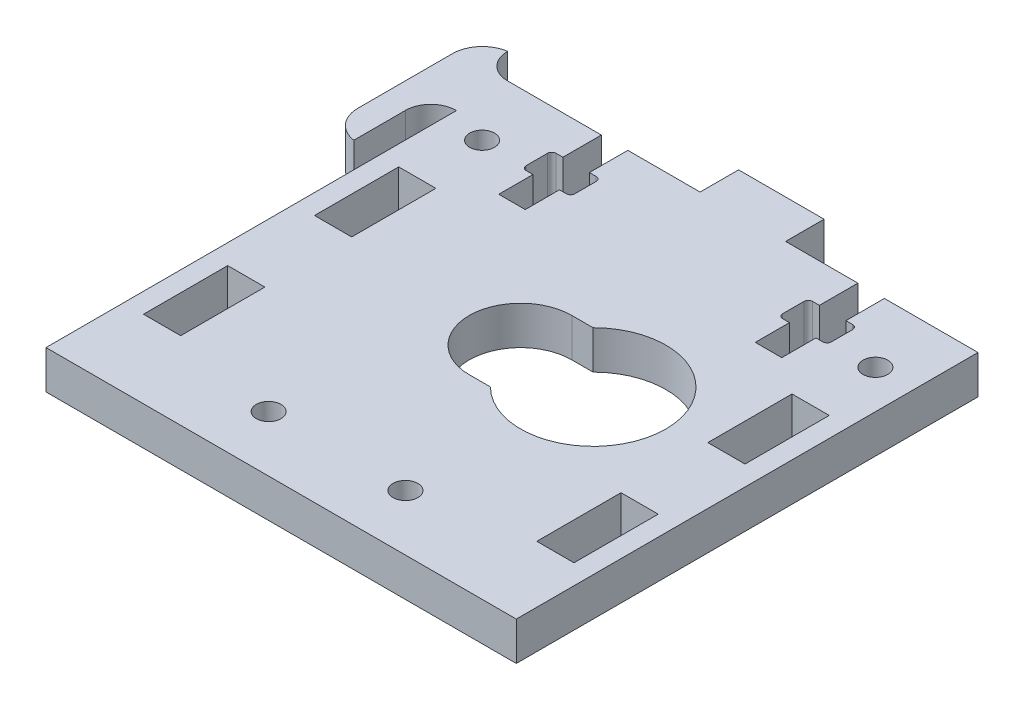
SolidWorks part; units mm, degrees
ref_plane "Front Plane" through (0, 0, 0) normal (0, 0, 1) x (1, 0, 0)
ref_plane "Top Plane" through (0, 0, 0) normal (0, 1, 0) x (1, 0, 0)
ref_plane "Right Plane" through (0, 0, 0) normal (1, 0, 0) x (0, 0, -1)
sketch "Sketch1" plane through (0, 0, 0) normal (0, 1, 0) x (1, 0, 0)
  line L1 (-27.5, 27) -> (27.5, 27)
  line L2 (-27.5, 27) -> (-27.5, -27)
  line L3 (-27.5, -27) -> (27.5, -27)
  line L4 (27.5, 27) -> (27.5, -27)
  line L5 (-27.5, 27) -> (27.5, -27) construction
  line L6 (-27.5, -27) -> (27.5, 27) construction
  point P0 (0, 0)
  dimension "D1" = 55
  dimension "D2" = 54
extrude "MainShape" add sketch "Sketch1" along normal blind 4.5
sketch "Sketch2" plane through (0, 4.5, 0) normal (0, 1, 0) x (1, 0, 0)
  line L0 (0, -27) -> (0, 27) construction
  line L1 (-27.5, -27) -> (27.5, -27) construction
  line L2 (27.5, 27) -> (-27.5, 27) construction
  line L4 (-5, 31.5) -> (5, 31.5)
  line L5 (-5, 31.5) -> (-5, 22.5)
  line L6 (-5, 22.5) -> (5, 22.5)
  line L7 (5, 31.5) -> (5, 22.5)
  line L8 (-5, 31.5) -> (5, 22.5) construction
  line L9 (-5, 22.5) -> (5, 31.5) construction
  dimension "D1" = 10
  dimension "D2" = 4.5
extrude "Tab1" add sketch "Sketch2" against normal through all
sketch "Sketch4" plane through (0, 4.5, 0) normal (0, 1, 0) x (1, 0, 0)
  line L0 (0, 31.5) -> (0, -27) construction
  line L1 (5, 31.5) -> (-5, 31.5) construction
  line L2 (-27.5, -27) -> (27.5, -27) construction
  line L3 (-15, 27) -> (-15, 15) construction
  line L4 (-5, 27) -> (-27.5, 27) construction
  line L5 (-13.45, 15) -> (-16.55, 15) construction
  line L6 (-16.55, 15) -> (-16.55, 27) construction
  line L7 (-13.45, 15) -> (-16.55, 15)
  line L8 (-16.55, 15) -> (-16.55, 19)
  line L9 (-16.55, 19) -> (-17.35, 19)
  line L10 (-17.85, 19.5) -> (-17.85, 22)
  line L11 (-17.35, 22.5) -> (-16.55, 22.5)
  line L12 (-16.55, 22.5) -> (-16.55, 27)
  line L13 (-16.55, 27) -> (-13.45, 27)
  line L14 (-13.45, 15) -> (-13.45, 27) construction
  line L15 (-13.45, 22.5) -> (-13.45, 27)
  line L16 (-12.65, 22.5) -> (-13.45, 22.5)
  line L17 (-12.15, 19.5) -> (-12.15, 22)
  line L18 (-13.45, 19) -> (-12.65, 19)
  line L19 (-13.45, 15) -> (-13.45, 19)
  line L20 (13.45, 15) -> (13.45, 27) construction
  line L21 (16.55, 15) -> (16.55, 27) construction
  line L22 (13.45, 15) -> (16.55, 15) construction
  line L23 (15, 27) -> (15, 15) construction
  line L24 (13.45, 15) -> (13.45, 19)
  line L25 (13.45, 19) -> (12.65, 19)
  line L26 (12.15, 19.5) -> (12.15, 22)
  line L27 (12.65, 22.5) -> (13.45, 22.5)
  line L28 (13.45, 22.5) -> (13.45, 27)
  line L29 (16.55, 27) -> (13.45, 27)
  line L30 (16.55, 22.5) -> (16.55, 27)
  line L31 (17.35, 22.5) -> (16.55, 22.5)
  line L32 (17.85, 19.5) -> (17.85, 22)
  line L33 (16.55, 19) -> (17.35, 19)
  line L34 (16.55, 15) -> (16.55, 19)
  line L35 (13.45, 15) -> (16.55, 15)
  arc A0 (-17.35, 19) -> (-17.85, 19.5) centre (-17.35, 19.5) cw
  arc A1 (-12.15, 19.5) -> (-12.65, 19) centre (-12.65, 19.5) cw
  arc A2 (-12.65, 22.5) -> (-12.15, 22) centre (-12.65, 22) cw
  arc A3 (-17.85, 22) -> (-17.35, 22.5) centre (-17.35, 22) cw
  arc A4 (17.85, 22) -> (17.35, 22.5) centre (17.35, 22) ccw
  arc A5 (12.65, 22.5) -> (12.15, 22) centre (12.65, 22) ccw
  arc A6 (12.15, 19.5) -> (12.65, 19) centre (12.65, 19.5) ccw
  arc A7 (17.35, 19) -> (17.85, 19.5) centre (17.35, 19.5) ccw
  point P24 (-17.85, 19)
  point P27 (-12.15, 19)
  point P30 (-12.15, 22.5)
  point P33 (-17.85, 22.5)
  point P56 (17.85, 22.5)
  point P57 (12.15, 22.5)
  point P58 (12.15, 19)
  point P59 (17.85, 19)
  dimension "D7" = 0.5
  dimension "D1" = 12
  dimension "D2" = 1.55
  dimension "D3" = 3.5
  dimension "D4" = 2.85
  dimension "D5" = 8
  dimension "D6" = 15
extrude "Cut-Extrude2" cut sketch "Sketch4" against normal through all
sketch "Sketch5" plane through (0, 4.5, 0) normal (0, 1, 0) x (1, 0, 0)
  line L0 (0, -27) -> (0, 31.5) construction
  line L1 (-27.5, -27) -> (27.5, -27) construction
  line L2 (5, 31.5) -> (-5, 31.5) construction
  line L3 (23, 27) -> (23, -27) construction
  line L4 (27.5, 27) -> (16.55, 27) construction
  line L5 (-23, 27) -> (-23, -27) construction
  line L6 (20.825, 11.925) -> (25.175, 11.925)
  line L7 (20.825, 11.925) -> (20.825, 2.075)
  line L8 (20.825, 2.075) -> (25.175, 2.075)
  line L9 (25.175, 11.925) -> (25.175, 2.075)
  line L10 (20.825, 11.925) -> (25.175, 2.075) construction
  line L11 (20.825, 2.075) -> (25.175, 11.925) construction
  line L12 (-20.825, 2.075) -> (-25.175, 11.925) construction
  line L13 (-20.825, 11.925) -> (-25.175, 2.075) construction
  line L14 (-25.175, 11.925) -> (-25.175, 2.075)
  line L15 (-20.825, 2.075) -> (-25.175, 2.075)
  line L16 (-20.825, 11.925) -> (-20.825, 2.075)
  line L17 (-20.825, 11.925) -> (-25.175, 11.925)
  line L18 (-27.5, -3) -> (27.5, -3) construction
  line L19 (-27.5, 27) -> (-27.5, -27) construction
  line L20 (27.5, -27) -> (27.5, 27) construction
  line L21 (-20.825, -17.925) -> (-25.175, -8.075) construction
  line L22 (-20.825, -8.075) -> (-25.175, -17.925) construction
  line L23 (20.825, -8.075) -> (25.175, -17.925) construction
  line L24 (20.825, -17.925) -> (25.175, -8.075) construction
  line L25 (-20.825, -17.925) -> (-25.175, -17.925)
  line L26 (-20.825, -17.925) -> (-20.825, -8.075)
  line L27 (-20.825, -8.075) -> (-25.175, -8.075)
  line L28 (-25.175, -17.925) -> (-25.175, -8.075)
  line L29 (25.175, -17.925) -> (25.175, -8.075)
  line L30 (20.825, -8.075) -> (25.175, -8.075)
  line L31 (20.825, -17.925) -> (20.825, -8.075)
  line L32 (20.825, -17.925) -> (25.175, -17.925)
  line L33 (-20.825, 11.925) -> (-25.175, 2.075) construction
  point P10 (23, 7)
  point P21 (-23, 7)
  point P36 (-23, -13)
  point P37 (23, -13)
  dimension "D1" = 23
  dimension "D2" = 9.85
  dimension "D3" = 4.35
  dimension "D4" = 20
  dimension "D5" = 20
extrude "Cut-Extrude3" cut sketch "Sketch5" against normal through all
sketch "Sketch6" plane through (0, 4.5, 0) normal (0, 1, 0) x (1, 0, 0)
  line L0 (0, -27) -> (0, 27) construction
  line L1 (5, 31.5) -> (-5, 31.5) construction
  line L3 (-27.5, 1) -> (27.5, 1) construction
  line L4 (-27.5, 27) -> (-27.5, -27) construction
  line L5 (27.5, -27) -> (27.5, 27) construction
  line L6 (27.5, 27) -> (16.55, 27) construction
  line L7 (-27.5, -27) -> (27.5, -27) construction
  line L9 (-27.5, 27) -> (27.5, 27) construction
  circle A0 centre (0, 1) radius 12
  point P4 (0, 31.5)
  dimension "D1" = 24
  dimension "D2" = 26
extrude "Cut-Extrude4" cut sketch "Sketch6" against normal through all
sketch "Sketch7" plane through (0, 4.5, 0) normal (0, 1, 0) x (1, 0, 0)
  line L0 (0, 1) -> (0, -27) construction
  line L3 (-27.5, -27) -> (27.5, -27) construction
  line L4 (8, -20.46) -> (-8, -20.46) construction
  circle A1 centre (-8, -20.46) radius 1.45
  circle A2 centre (8, -20.46) radius 1.45
  point P8 (0, -20.46)
  dimension "D1" = 2.9
  dimension "D3" = 21.46
extrude "Cut-Extrude5" [suppressed] cut sketch "Sketch7" against normal through all
sketch "Sketch8" plane through (0, 4.5, 0) normal (0, 1, 0) x (1, 0, 0)
  line L0 (-12, 1) -> (12, 1) construction
  line L1 (0, 1) -> (0, -20.46) construction
  line L2 (8, -20.46) -> (-8, -20.46) construction
  line L3 (0, -11) -> (0, 13) construction
  circle A0 centre (-8, -20.46) radius 1.45
  circle A1 centre (0, 1) radius 12 construction
  circle A2 centre (8, -20.46) radius 1.45
  dimension "D3" = 2.9
  dimension "D1" = 90
  dimension "D4" = 21.46
extrude "Cut-Extrude6" cut sketch "Sketch8" against normal through all
sketch "Sketch9" plane through (0, 4.5, 0) normal (0, 1, 0) x (1, 0, 0)
  line L0 (0, -27) -> (0, 31.5) construction
  line L1 (-27.5, -27) -> (27.5, -27) construction
  line L2 (5, 31.5) -> (-5, 31.5) construction
  line L3 (16, -27) -> (16, -16) construction
  line L4 (14.45, -16) -> (17.55, -16) construction
  line L5 (17.55, -16) -> (17.55, -27) construction
  line L6 (17.55, -27) -> (17.55, -22.5)
  line L7 (17.55, -22.5) -> (18.35, -22.5)
  line L8 (18.85, -22) -> (18.85, -19.5)
  line L9 (18.35, -19) -> (17.55, -19)
  line L10 (17.55, -19) -> (17.55, -16)
  line L11 (17.55, -16) -> (14.45, -16)
  line L12 (17.55, -27) -> (14.45, -27)
  line L13 (14.45, -16) -> (14.45, -27) construction
  line L14 (14.45, -19) -> (14.45, -16)
  line L15 (13.65, -19) -> (14.45, -19)
  line L16 (13.15, -22) -> (13.15, -19.5)
  line L17 (14.45, -22.5) -> (13.65, -22.5)
  line L18 (14.45, -27) -> (14.45, -22.5)
  line L19 (-14.45, -16) -> (-14.45, -27) construction
  line L20 (-17.55, -16) -> (-17.55, -27) construction
  line L21 (-14.45, -16) -> (-17.55, -16) construction
  line L22 (-16, -27) -> (-16, -16) construction
  line L23 (-14.45, -27) -> (-14.45, -22.5)
  line L24 (-14.45, -22.5) -> (-13.65, -22.5)
  line L25 (-13.15, -22) -> (-13.15, -19.5)
  line L26 (-13.65, -19) -> (-14.45, -19)
  line L27 (-14.45, -19) -> (-14.45, -16)
  line L28 (-17.55, -27) -> (-14.45, -27)
  line L29 (-17.55, -16) -> (-14.45, -16)
  line L30 (-17.55, -19) -> (-17.55, -16)
  line L31 (-18.35, -19) -> (-17.55, -19)
  line L32 (-18.85, -22) -> (-18.85, -19.5)
  line L33 (-17.55, -22.5) -> (-18.35, -22.5)
  line L34 (-17.55, -27) -> (-17.55, -22.5)
  arc A0 (18.35, -22.5) -> (18.85, -22) centre (18.35, -22) ccw
  arc A1 (18.85, -19.5) -> (18.35, -19) centre (18.35, -19.5) ccw
  arc A2 (13.15, -19.5) -> (13.65, -19) centre (13.65, -19.5) cw
  arc A3 (13.65, -22.5) -> (13.15, -22) centre (13.65, -22) cw
  arc A4 (-13.65, -22.5) -> (-13.15, -22) centre (-13.65, -22) ccw
  arc A5 (-13.15, -19.5) -> (-13.65, -19) centre (-13.65, -19.5) ccw
  arc A6 (-18.85, -19.5) -> (-18.35, -19) centre (-18.35, -19.5) cw
  arc A7 (-18.35, -22.5) -> (-18.85, -22) centre (-18.35, -22) cw
  point P16 (18.85, -22.5)
  point P19 (18.85, -19)
  point P30 (13.15, -19)
  point P31 (13.15, -22.5)
  point P54 (-13.15, -22.5)
  point P55 (-13.15, -19)
  point P56 (-18.85, -19)
  point P57 (-18.85, -22.5)
  dimension "D7" = 0.5
  dimension "D2" = 1.55
  dimension "D1" = 11
  dimension "D3" = 8
  dimension "D4" = 3.5
  dimension "D5" = 2.85
  dimension "D6" = 16
extrude "Cut-Extrude7" [suppressed] cut sketch "Sketch9" against normal through all
sketch "Sketch10" [suppressed] plane through (0, 0, 27) normal (0, 0, 1) x (1, 0, 0)
  line L0 (-27.5, 2.25) -> (27.5, 2.25) construction
  line L1 (-27.5, 4.5) -> (-27.5, 0) construction
  line L2 (27.5, 4.5) -> (27.5, 0) construction
  line L3 (-16, 4.5) -> (-16, 0) construction
  line L4 (-14.25, 4.5) -> (-17.75, 4.5) construction
  line L5 (16, 4.5) -> (16, 0) construction
  line L6 (17.75, 4.5) -> (14.25, 4.5) construction
  line L7 (17.75, 0) -> (14.25, 0) construction
  line L8 (-14.25, 0) -> (-17.75, 0) construction
  circle A0 centre (-16, 2.25) radius 1.6
  circle A1 centre (16, 2.25) radius 1.6
  dimension "D1" = 3.2
  dimension "D2" = 3.2
sketch "Sketch11" plane through (0, 4.5, 0) normal (0, 1, 0) x (1, 0, 0)
  line L0 (-20.825, 7) -> (-25.175, 7) construction
  line L1 (-20.825, 2.075) -> (-20.825, 11.925) construction
  line L2 (-25.175, 11.925) -> (-25.175, 2.075) construction
  line L3 (-23, 7) -> (-23, 27) construction
  line L4 (-16.55, 27) -> (-27.5, 27) construction
  line L5 (0, 31.5) -> (0, 0) construction
  line L6 (5, 31.5) -> (-5, 31.5) construction
  line L7 (23, 7) -> (23, 27) construction
  line L8 (20.825, 7) -> (25.175, 7) construction
  line L9 (-23, 7) -> (-23, 27) construction
  circle A0 centre (-23, 19.5) radius 1.45
  circle A1 centre (23, 19.5) radius 1.45
  dimension "D1" = 2.9
  dimension "D2" = 7.5
extrude "Cut-Extrude8" cut sketch "Sketch11" against normal through all
sketch "Sketch12" [suppressed] plane through (0, 4.5, 0) normal (0, 1, 0) x (1, 0, 0)
  line L0 (-27.5, -7) -> (-34, -17)
  line L1 (-27.5, 27) -> (-27.5, -27) construction
  line L2 (-34, -17) -> (-34, -27)
  line L3 (-34, -27) -> (-27.5, -27)
  line L4 (-27.5, -27) -> (-27.5, -7)
  line L5 (-27.5, -27) -> (27.5, -27) construction
  line L6 (0, -27) -> (0, 31.5) construction
  line L7 (5, 31.5) -> (-5, 31.5) construction
  line L8 (27.5, -27) -> (27.5, -7)
  line L9 (34, -27) -> (27.5, -27)
  line L10 (34, -17) -> (34, -27)
  line L11 (27.5, -7) -> (34, -17)
  point P4 (0, -27)
  dimension "D1" = 34
  dimension "D2" = 10
  dimension "D3" = 20
extrude "Boss-Extrude1" [suppressed] add sketch "Sketch12" against normal through all
sketch "Sketch14" [suppressed] plane through (0, 4.5, 0) normal (0, 1, 0) x (1, 0, 0)
  line L0 (-34, -27) -> (34, -27) construction
  line L2 (-34, -27) -> (34, -27) construction
  line L3 (0, -27) -> (0, 31.5) construction
  line L4 (5, 31.5) -> (-5, 31.5) construction
  line L6 (26.25, -16.5) -> (26.25, -27) construction
  line L8 (-28, -27) -> (-28, -16.5) construction
  line L9 (-26.25, -16.5) -> (-29.75, -16.5) construction
  line L10 (-29.75, -16.5) -> (-29.75, -27) construction
  line L11 (-26.25, -27) -> (-29.75, -27)
  line L12 (-29.75, -27) -> (-29.75, -23.2)
  line L13 (-29.75, -23.2) -> (-30.75, -23.2)
  line L14 (-31, -22.95) -> (-31, -19.25)
  line L15 (-30.75, -19) -> (-29.75, -19)
  line L16 (-29.75, -19) -> (-29.75, -16.5)
  line L17 (-29.75, -16.5) -> (-26.25, -16.5)
  line L18 (-26.25, -16.5) -> (-26.25, -27) construction
  line L19 (-26.25, -19) -> (-26.25, -16.5)
  line L20 (-25.25, -19) -> (-26.25, -19)
  line L21 (-25, -22.95) -> (-25, -19.25)
  line L22 (-26.25, -23.2) -> (-25.25, -23.2)
  line L23 (-26.25, -27) -> (-26.25, -23.2)
  line L24 (29.75, -16.5) -> (29.75, -27) construction
  line L25 (26.25, -16.5) -> (29.75, -16.5) construction
  line L26 (28, -27) -> (28, -16.5) construction
  line L27 (26.25, -27) -> (26.25, -23.2)
  line L28 (26.25, -23.2) -> (25.25, -23.2)
  line L29 (25, -22.95) -> (25, -19.25)
  line L30 (25.25, -19) -> (26.25, -19)
  line L31 (26.25, -19) -> (26.25, -16.5)
  line L32 (29.75, -16.5) -> (26.25, -16.5)
  line L33 (29.75, -19) -> (29.75, -16.5)
  line L34 (30.75, -19) -> (29.75, -19)
  line L35 (31, -22.95) -> (31, -19.25)
  line L36 (29.75, -23.2) -> (30.75, -23.2)
  line L37 (29.75, -27) -> (29.75, -23.2)
  line L38 (26.25, -27) -> (29.75, -27)
  line L39 (-26.25, -16.5) -> (-26.25, -27) construction
  arc A0 (-30.75, -23.2) -> (-31, -22.95) centre (-30.75, -22.95) cw
  arc A1 (-31, -19.25) -> (-30.75, -19) centre (-30.75, -19.25) cw
  arc A2 (-25, -19.25) -> (-25.25, -19) centre (-25.25, -19.25) ccw
  arc A3 (-25.25, -23.2) -> (-25, -22.95) centre (-25.25, -22.95) ccw
  arc A4 (25.25, -23.2) -> (25, -22.95) centre (25.25, -22.95) cw
  arc A5 (25, -19.25) -> (25.25, -19) centre (25.25, -19.25) cw
  arc A6 (31, -19.25) -> (30.75, -19) centre (30.75, -19.25) ccw
  arc A7 (30.75, -23.2) -> (31, -22.95) centre (30.75, -22.95) ccw
  point P2 (0, -27)
  dimension "D10" = 0.5
  dimension "D4" = 1.55
  dimension "D6" = 11
  dimension "D2" = 28
  dimension "D3" = 2.85
  dimension "D5" = 3.5
  dimension "D7" = 8
extrude "Cut-Extrude9" [suppressed] cut sketch "Sketch14" against normal through all
sketch "Sketch15" plane through (0, 4.5, 0) normal (0, 1, 0) x (1, 0, 0)
  circle A0 centre (0, 1) radius 12
  circle A1 centre (0, 1) radius 6
  circle A2 centre (0, 1) radius 12 construction
  dimension "D1" = 12
extrude "Boss-Extrude2" add sketch "Sketch15" against normal through all
sketch "Sketch16" plane through (0, 4.5, 0) normal (0, 1, 0) x (1, 0, 0)
  line L0 (0, 1) -> (27.5, 1) construction
  line L1 (27.5, -27) -> (27.5, 27) construction
  line L2 (0, 7) -> (2.4792, 7)
  line L3 (0, -5) -> (2.4792, -5)
  line L4 (0, 7) -> (0, -5)
  arc A0 (2.4792, -5) -> (2.4792, 7) centre (8.5, 1) ccw
  circle A1 centre (0, 1) radius 6 construction
  dimension "D1" = 17
  dimension "D2" = 8.5
extrude "Cut-Extrude10" cut sketch "Sketch16" against normal through all
sketch "Sketch17" plane through (0, 4.5, 0) normal (0, 1, 0) x (1, 0, 0)
  line L0 (-27.5, 22) -> (-27.5, 18) construction
  line L1 (-27.5, 27) -> (-27.5, -27) construction
  line L2 (-27.5, 25.5) -> (-27.5, 23.5)
  line L3 (-29, 22) -> (-29, 18)
  line L4 (-27.5, 22) -> (-27.5, 18) construction
  line L5 (-27.5, 16.5) -> (-27.5, 14.5)
  line L6 (-31, 22) -> (-31, 18)
  line L7 (-27.5, 25.5) -> (-27.5, 14.5) construction
  arc A0 (-27.5, 23.5) -> (-29, 22) centre (-27.5, 22) ccw
  arc A1 (-29, 18) -> (-27.5, 16.5) centre (-27.5, 18) ccw
  arc A2 (-27.5, 25.5) -> (-31, 22) centre (-27.5, 22) ccw
  arc A3 (-31, 18) -> (-27.5, 14.5) centre (-27.5, 18) ccw
  point P10 (-27.5, 20)
  dimension "D1" = 1.5
  dimension "D2" = 1.5
  dimension "D3" = 2
  dimension "D4" = 4
  dimension "D5" = 20
  dimension "D7" = 2
extrude "CableTieSlot" [suppressed] add sketch "Sketch17" against normal through all
sketch "Sketch18" plane through (0, 4.5, 0) normal (0, 1, 0) x (1, 0, 0)
  line L0 (-27.5, 27) -> (-27.55, 27)
  line L1 (-33.5, 30) -> (-33.5, 12)
  line L2 (-33.5, 12) -> (-30.5, 12)
  line L3 (-30.5, 12) -> (-30.5, 18.05)
  line L4 (-27.55, 21) -> (-27.5, 21)
  line L5 (-27.5, 27) -> (-27.5, -27) construction
  line L6 (-27.5, 21) -> (-27.5, 27)
  line L7 (-16.55, 27) -> (-27.5, 27) construction
  line L8 (-33.5, 30) -> (-30.5, 30)
  line L9 (-30.5, 30) -> (-30.5, 29.95)
  arc A0 (-27.55, 27) -> (-30.5, 29.95) centre (-27.55, 29.95) cw
  arc A1 (-30.5, 18.05) -> (-27.55, 21) centre (-27.55, 18.05) cw
  point P17 (-30.5, 27)
  dimension "D1" = 2.95
  dimension "D2" = 2.95
  dimension "D3" = 6
  dimension "D4" = 3
  dimension "D5" = 15
  dimension "D6" = 3
  dimension "D7" = 3
extrude "Boss-Extrude3" add sketch "Sketch18" against normal through all
fillet "Fillet1" radius 3.5 2 edges at (-33.5, 2.25, -30) (-33.5, 2.25, -12)
equation "\"X-ROD-SPACING\"=45"
equation "\"Y-ROD-SPACING\"=75"
equation "\"Z-ROD-SPACING\"=17.5"
equation "\"Y-BED-OFFSET\"=2"
equation "\"Y-BED-ROD-INSET\"=3.5"
equation "\"Y-BED-SCREW-SPACING\"=209"
equation "\"Y-BED-SCREW-CUTOUT-SLOT-HEIGHT\"=2.5"
equation "\"T-SLOT-NUT-FILLET-RADIUS\"=0.5"
equation "\"T-SLOT-SCREW-SHAFT-RADIUS\"=1.55"
equation "\"T-SLOT-SCREW-SHAFT-CUTOUT-LENGTH\"=11"
equation "\"T-SLOT-NUT-DEPTH\"=3.5"
equation "\"T-SLOT-NUT-WIDTH\"=2.85"
equation "\"T-SLOT-NUT-END-DISTANCE\"=8"
equation "\"ACRYLIC-THICKNESS\"=10"
equation "\"ACRYLIC-THICKNESS2\"=4.5"
equation "\"ACRYLIC-TAB-CUTOUT-SIZE\"=\"ACRYLIC-THICKNESS\"+\"ACRYLIC-TAB-TOLERANCE\"*2"
equation "\"ACRYLIC-TAB-WIDTH\"=\"ACRYLIC-THICKNESS\""
equation "\"ACRYLIC-M3-HOLE\"=2.9"
equation "\"SMOOTHROD-CAP-SCREW-DISTANCE\"=20"
equation "\"FRAME-WIDTH-INNER\"=370"
equation "\"NEMA17-HOLE-SPACING\"=31"
equation "\"NEMA17-CENTRAL-CUTOUT\"=22.5"
equation "\"Z-BRACKET-REACH\"=57"
equation "\"Z-ROD-INSET\"=13.5"
equation "\"TOP-BRACKET-SPACING\"=40"
equation "\"SMOOTHROD-X-LENGTH\"=350"
equation "\"SMOOTHROD-Y-LENGTH\"=350"
equation "\"SMOOTHROD-Z-LENGTH\"=350"
equation "\"SMOOTHROD-TIGHTENING-HEADROOM\"=.25"
equation "\"LEADSCREW-Z-LENGTH\"=300"
equation "\"SCREW-LENGTH-FRAME\"=\"ACRYLIC-THICKNESS\" + 10"
equation "\"SCREW-LENGTH-MOTOR\"=\"ACRYLIC-THICKNESS\" + 5"
equation "\"SCREW-LENGTH-EXTRUDER\"=28"
equation "\"SCREW-HEAD-RADIUS\"=6"
equation "\"PRINTED-X-SMOOTHROD-DIAMETER\"=8.8"
equation "\"PRINTED-X-SMOOTHROD-CUTOUT\"=10"
equation "\"PRINTED-X-BASE-HEIGHT\"=10"
equation "\"PRINTED-LM8UU-CUTOUT-SIZE\"=15.5"
equation "\"PRINTED-LM8UU-CUTOUT-LENGTH\"=24.5"
equation "\"PRINTED-X-IDLER-HEIGHT\"=16"
equation "\"PSU-MOUNTING-WIDTH\"=50"
equation "\"PSU-MOUNTING-HEIGHT\"=150"
equation "\"Y-BELT-TO-ROD-DISTANCE\"=20"
equation "\"SPOOL-HOLDER-ROD-SPACING\"=150"
equation "\"ACRYLIC-X-CARRIAGE-WIDTH\"=55"
equation "\"ACRYLIC-X-CARRIAGE-HEIGHT\"=75"
equation "\"ACRYLIC-X-CARRIAGE-SCREW-SPACING-X\"=15"
equation "\"ACRYLIC-X-CARRIAGE-SCREW-SPACING-Y\"=33"
equation "\"ACRYLIC-X-CARRIAGE-CENTER-TAB-SPACING\"=14"
equation "\"D1@Sketch1\"=\"ACRYLIC-X-CARRIAGE-WIDTH\""
equation "\"D1@MainShape\" = \"ACRYLIC-THICKNESS2\""
equation "\"D1@Sketch2\"=\"ACRYLIC-TAB-WIDTH\""
equation "\"D2@Sketch2\"=\"ACRYLIC-THICKNESS2\""
equation "\"D1@Sketch4\"=\"T-SLOT-SCREW-SHAFT-CUTOUT-LENGTH\"+1"
equation "\"D2@Sketch4\"=\"T-SLOT-SCREW-SHAFT-RADIUS\""
equation "\"D3@Sketch4\"=\"T-SLOT-NUT-DEPTH\""
equation "\"D4@Sketch4\"=\"T-SLOT-NUT-WIDTH\""
equation "\"D5@Sketch4\"=\"T-SLOT-NUT-END-DISTANCE\""
equation "\"D6@Sketch4\"=\"ACRYLIC-X-CARRIAGE-SCREW-SPACING-X\""
equation "\"D7@Sketch4\"=\"T-SLOT-NUT-FILLET-RADIUS\""
equation "\"ACRYLIC-X-CARRIAGE-EXTRUDER-SHELF-DEPTH\"=\"ACRYLIC-X-CARRIAGE-EXTRUDER-OFFSET\" + 28"
equation "\"D2@Sketch1\"=\"ACRYLIC-X-CARRIAGE-EXTRUDER-SHELF-DEPTH\""
equation "\"ACRYLIC-X-CARRIAGE-LM8UU-CUTOUT-WIDTH\"=24.25"
equation "\"ACRYLIC-X-CARRIAGE-EXTRUDER-BRACE-SPACING\"=23"
equation "\"ACRYLIC-X-CARRIAGE-EXTRUDER-BRACE-TAB-OFFSET\"=20"
equation "\"ACRYLIC-X-CARRIAGE-EXTRUDER-BRACE-HEIGHT\"=35"
equation "\"ACRYLIC-X-CARRIAGE-EXTRUDER-BRACE-SCREW-SPACING\"=22"
equation "\"D1@Sketch5\"=\"ACRYLIC-X-CARRIAGE-EXTRUDER-BRACE-SPACING\""
equation "\"D2@Sketch5\"=\"ACRYLIC-TAB-WIDTH\"-\"KERF\"*2"
equation "\"D3@Sketch5\"=\"ACRYLIC-THICKNESS2\"-\"KERF\"*2"
equation "\"D4@Sketch5\"=\"ACRYLIC-X-CARRIAGE-EXTRUDER-BRACE-TAB-OFFSET\""
equation "\"D1@Sketch7\"=\"ACRYLIC-M3-HOLE\""
equation "\"D3@Sketch8\"=\"ACRYLIC-M3-HOLE\""
equation "\"ACRYLIC-X-CARRIAGE-EXTRUDER-ANGLE\"=90"
equation "\"D1@Sketch8\"=\"ACRYLIC-X-CARRIAGE-EXTRUDER-ANGLE\""
equation "\"ACRYLIC-X-CARRIAGE-EXTRUDER-OFFSET\"=26"
equation "\"D2@Sketch6\"=\"ACRYLIC-X-CARRIAGE-EXTRUDER-OFFSET\""
equation "\"D1@Sketch9\"=\"T-SLOT-SCREW-SHAFT-CUTOUT-LENGTH\""
equation "\"D2@Sketch9\"=\"T-SLOT-SCREW-SHAFT-RADIUS\""
equation "\"D3@Sketch9\"=\"T-SLOT-NUT-END-DISTANCE\""
equation "\"D4@Sketch9\"=\"T-SLOT-NUT-DEPTH\""
equation "\"D5@Sketch9\"=\"T-SLOT-NUT-WIDTH\""
equation "\"D7@Sketch9\"=\"T-SLOT-NUT-FILLET-RADIUS\""
equation "\"ACRYLIC-TAB-TOLERANCE\"=-.05"
equation "\"D1@Sketch11\"=\"ACRYLIC-M3-HOLE\""
equation "\"D6@Sketch14\"=\"T-SLOT-SCREW-SHAFT-CUTOUT-LENGTH\""
equation "\"D3@Sketch14\"=\"T-SLOT-NUT-WIDTH\""
equation "\"D5@Sketch14\"=\"T-SLOT-NUT-DEPTH\""
equation "\"D4@Sketch14\"=\"T-SLOT-SCREW-SHAFT-RADIUS\""
equation "\"D10@Sketch14\"=\"T-SLOT-NUT-FILLET-RADIUS\""
equation "\"D7@Sketch14\"=\"T-SLOT-NUT-END-DISTANCE\""
equation "\"KERF\"=0.075"
equation "\"PRINTED-M3-HOLE\"=3.5"
equation "\"PRINTED-M3-NUT-AF\"=6.25"
equation "\"ACRYLIC-X-CARRIAGE-LM8UU-CUTOUT-HEIGHT\"=11.0"
equation "\"ACRYLIC-X-CARRIAGE-DUAL-WIDTH-MULTIPLIER\"=1.65"
equation "\"ACRYLIC-X-CARRIAGE-DUAL-HOTEND-SPACING\"=42"
equation "\"ACRYLIC-X-CARRIAGE-DUAL-WIDTH\"=75"
equation "\"ACRYLIC-X-CARRIAGE-DUAL-FAN-OFFSET\"=52"
equation "\"ACRYLIC-X-CARRIAGE-DUAL-FAN-HEIGHT\"=20"
equation "\"ACRYLIC-X-CARRIAGE-DUAL-HOTEND-SEPARATION\"=36"
equation "\"ACRYLIC-X-CARRIAGE-DUAL-MOUNT-PLATE-DEPTH\"=75"
equation "\"ACRYLIC-X-CARRIAGE-DUAL-MOUNT-BRACE-WIDTH\"=33"
equation "\"ACRYLIC-X-CARRIAGE-DUAL-MOUNT-SCREW-WIDTH\"=40"
equation "\"BLOWER-FAN-WIDTH\"=15"
